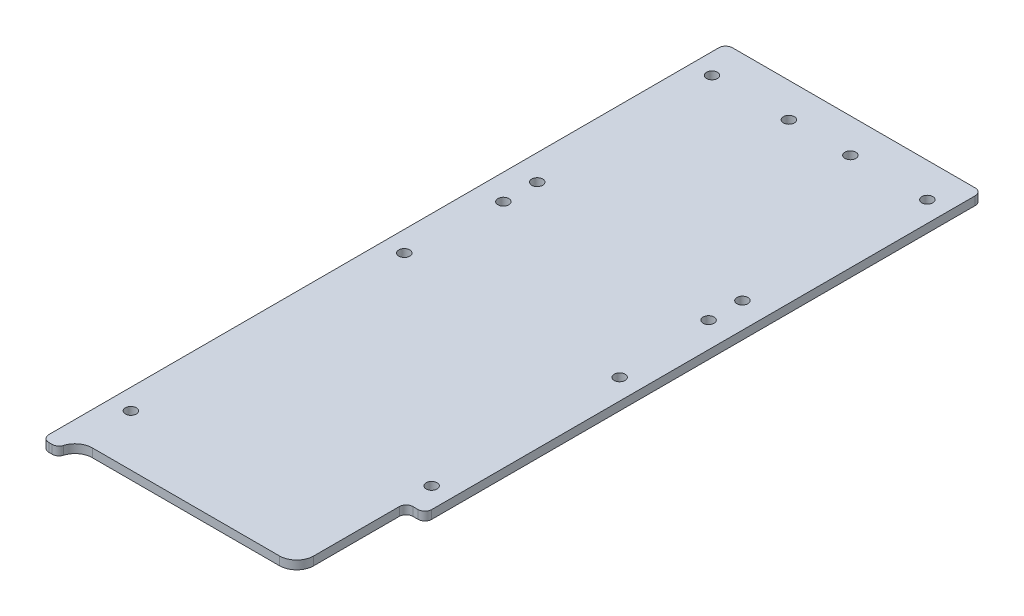
SolidWorks part; units mm, degrees
ref_plane "Front Plane" through (0, 0, 0) normal (0, 0, 1) x (1, 0, 0)
ref_plane "Top Plane" through (0, 0, 0) normal (0, 1, 0) x (1, 0, 0)
ref_plane "Right Plane" through (0, 0, 0) normal (1, 0, 0) x (0, 0, -1)
sketch "Sketch1" plane through (0, 0, 0) normal (0, 1, 0) x (1, 0, 0)
  line L0 (-39.9997, 0) -> (-39.9997, 114.3) construction
  line L1 (-47.625, 127) -> (47.625, 127)
  line L2 (-47.625, 127) -> (-47.625, -127)
  line L3 (-47.625, -127) -> (47.625, -127)
  line L4 (47.625, 127) -> (47.625, -127)
  line L5 (-47.625, 127) -> (47.625, -127) construction
  line L6 (-47.625, -127) -> (47.625, 127) construction
  line L7 (0, 0) -> (0, 127) construction
  line L8 (-39.9997, 0) -> (-39.9997, -101.6) construction
  line L9 (-39.9997, 0) -> (0, 0) construction
  line L10 (-41.275, -127) -> (-41.275, -120.65)
  line L11 (-41.275, -120.65) -> (41.275, -120.65)
  line L12 (41.275, -120.65) -> (41.275, -127)
  line L13 (-39.9997, 114.3) -> (-11.4247, 114.3) construction
  line L14 (39.9997, 114.3) -> (11.4247, 114.3) construction
  circle A0 centre (-39.9997, 114.3) radius 2.032
  circle A1 centre (-39.9997, 0) radius 2.032
  circle A2 centre (-39.9997, -101.6) radius 2.032
  circle A3 centre (39.9997, -101.6) radius 2.032
  circle A4 centre (39.9997, 0) radius 2.032
  circle A5 centre (39.9997, 114.3) radius 2.032
  circle A6 centre (-11.4247, 114.3) radius 2.032
  circle A7 centre (11.4247, 114.3) radius 2.032
  circle A8 centre (-39.9997, -69.85) radius 2.032
  circle A9 centre (39.9997, -69.85) radius 2.032
  point P0 (0, 0)
  dimension "D4" = 4.064
  dimension "D10" = 28.575
  dimension "D1" = 95.25
  dimension "D2" = 254
  dimension "D3" = 7.6253
  dimension "D5" = 12.7
  dimension "D6" = 25.4
  dimension "D7" = 6.35
  dimension "D8" = 6.35
  dimension "D9" = 6.35
  dimension "D11" = 69.85
extrude "Boss-Extrude1" add sketch "Sketch1" along normal blind 3.175 contours L4 L1 L2 L3 A4 A0 A1 A2 A3 A5 | A8 | A3 region at (0, 0, -2.6944) region at (39.9997, 0, 101.6) region at (-39.9997, 0, 69.85)
fillet "Fillet1" radius 2.54 4 edges at (-47.625, 1.5875, -127) (47.625, 1.5875, -127) (47.625, 1.5875, 127) (-47.625, 1.5875, 127)
fillet "Fillet2" radius 2.54 2 edges at (41.275, 1.5875, 127) (-41.275, 1.5875, 127)
fillet "Fillet3" radius 6.35 2 edges at (41.275, 1.5875, 120.65) (-41.275, 1.5875, 120.65)
sketch "Sketch2" plane through (0, 0, 0) normal (0, -1, 0) x (1, 0, 0)
  line L0 (41.9102, 131.8831) -> (41.9102, 109.8659) construction
  line L1 (41.9102, 109.8659) -> (41.9102, 106.3879) construction
  line L2 (41.9102, 83.271) -> (41.9102, 82.5325) construction
  line L3 (41.9102, 82.5325) -> (41.9102, 81.2514) construction
  line L4 (41.9102, 83.271) -> (41.9102, 106.3879) construction
  line L5 (41.9102, 131.8831) -> (41.9102, 109.8659)
  line L6 (41.9102, 109.8659) -> (41.9102, 106.3879)
  line L7 (41.9102, 83.271) -> (41.9102, 82.5325)
  line L8 (41.9102, 82.5325) -> (41.9102, 81.2514)
  line L9 (41.9102, 83.271) -> (41.9102, 106.3879)
  line L10 (41.9102, 81.2514) -> (47.625, 81.2514)
  line L11 (47.625, -124.46) -> (47.625, 124.46) construction
  line L12 (41.9102, 131.8831) -> (47.625, 131.8831)
  line L13 (47.625, 131.8831) -> (47.625, 81.2514)
  line L14 (40.6402, 79.9814) -> (48.895, 79.9814)
  line L15 (48.895, 133.1531) -> (48.895, 79.9814)
  line L16 (40.6402, 133.1531) -> (48.895, 133.1531)
  line L17 (40.6402, 133.1531) -> (40.6402, 109.8659)
  line L18 (40.6402, 109.8659) -> (40.6402, 106.3879)
  line L19 (40.6402, 83.271) -> (40.6402, 106.3879)
  line L20 (40.6402, 83.271) -> (40.6402, 82.5325)
  line L21 (40.6402, 82.5325) -> (40.6402, 79.9814)
  arc M7 (43.815, 127) -> (41.3809, 125.1857) centre (43.815, 124.46) ccw
  arc M8 (41.3809, 125.1857) -> (35.2956, 120.65) centre (35.2956, 127) cw
  line M18 (47.625, -124.46) -> (47.625, 124.46)
  dimension "D1" = 1.27
extrude "Cut-Extrude1" cut sketch "Sketch2" against normal through all contours L20 L21 L14 L10 L8 L7 L9 L19 M18 | L19 L9 L6 L5 L17 L18 M7 M8 | L13 L10 L8 L7 L9 L6 L5 L12 region at (41.6754, 0, 99.979)
fillet "Fillet4" radius 6.35 1 edges at (40.6402, 1.5875, 123.571)
fillet "Fillet5" radius 2.54 2 edges at (47.625, 1.5875, 79.9814) (40.6402, 1.5875, 79.9814)
sketch "Sketch3" plane through (0, 0, 0) normal (0, -1, 0) x (1, 0, 0)
  line L0 (-36.3103, -49.7791) -> (-39.9171, -49.7791) construction
  line L1 (-40.4251, -49.276) -> (-40.4251, -45.7043) construction
  line L2 (-35.8023, -45.7043) -> (-35.8023, -49.276) construction
  line L3 (-39.9171, -45.2013) -> (-36.3103, -45.2013) construction
  line L4 (-36.3103, -37.2027) -> (-39.9171, -37.2027) construction
  line L5 (-35.8023, -33.1279) -> (-35.8023, -36.6996) construction
  line L6 (-40.4251, -36.6996) -> (-40.4251, -33.1279) construction
  line L7 (-39.9171, -32.6249) -> (-36.3103, -32.6249) construction
  line L8 (36.2829, -32.6249) -> (39.8897, -32.6249) construction
  line L9 (40.3977, -33.1279) -> (40.3977, -36.6996) construction
  line L10 (39.8897, -37.2027) -> (36.2829, -37.2027) construction
  line L11 (35.7749, -36.6996) -> (35.7749, -33.1279) construction
  line L12 (36.2829, -45.2013) -> (39.8897, -45.2013) construction
  line L13 (35.7749, -49.276) -> (35.7749, -45.7043) construction
  line L14 (40.3977, -45.7043) -> (40.3977, -49.276) construction
  line L15 (39.8897, -49.7791) -> (36.2829, -49.7791) construction
  line L16 (-36.3103, -49.7791) -> (-39.9171, -49.7791)
  line L17 (-40.4251, -49.276) -> (-40.4251, -45.7043)
  line L18 (-35.8023, -45.7043) -> (-35.8023, -49.276)
  line L19 (-39.9171, -45.2013) -> (-36.3103, -45.2013)
  line L20 (-36.3103, -37.2027) -> (-39.9171, -37.2027)
  line L21 (-35.8023, -33.1279) -> (-35.8023, -36.6996)
  line L22 (-40.4251, -36.6996) -> (-40.4251, -33.1279)
  line L23 (-39.9171, -32.6249) -> (-36.3103, -32.6249)
  line L24 (36.2829, -32.6249) -> (39.8897, -32.6249)
  line L25 (40.3977, -33.1279) -> (40.3977, -36.6996)
  line L26 (39.8897, -37.2027) -> (36.2829, -37.2027)
  line L27 (35.7749, -36.6996) -> (35.7749, -33.1279)
  line L28 (36.2829, -45.2013) -> (39.8897, -45.2013)
  line L29 (35.7749, -49.276) -> (35.7749, -45.7043)
  line L30 (40.3977, -45.7043) -> (40.3977, -49.276)
  line L31 (39.8897, -49.7791) -> (36.2829, -49.7791)
  line L32 (-47.625, -25.836) -> (47.625, -25.836)
  line L33 (-47.625, -124.46) -> (-47.625, 124.46) construction
  line L34 (47.625, -124.46) -> (47.625, 77.4414) construction
  line L35 (0, -25.836) -> (0, -56.0686) construction
  line L38 (134.3604, -51.414) -> (184.1363, -51.414)
  line L39 (184.1363, -51.414) -> (184.1363, -43.4909)
  line L40 (184.1363, -43.4909) -> (182.3329, -43.4909)
  line L41 (181.8249, -42.9878) -> (181.8249, -39.4161)
  line L42 (182.3329, -38.9131) -> (184.1363, -38.9131)
  line L43 (184.1363, -38.9131) -> (184.1363, -30.9899)
  line L44 (184.1363, -30.9899) -> (134.3604, -30.9899)
  line L45 (134.3604, -30.9899) -> (133.3363, -32.0042)
  line L46 (133.3363, -32.0042) -> (132.3121, -30.9899)
  line L47 (132.3121, -30.9899) -> (70.8604, -30.9899)
  line L48 (70.8604, -30.9899) -> (69.8363, -32.0042)
  line L49 (69.8363, -32.0042) -> (68.8121, -30.9899)
  line L50 (68.8121, -30.9899) -> (7.3604, -30.9899)
  line L51 (7.3604, -30.9899) -> (6.3363, -32.0042)
  line L52 (6.3363, -32.0042) -> (5.3121, -30.9899)
  line L53 (5.3121, -30.9899) -> (-56.1396, -30.9899)
  line L54 (-56.1396, -30.9899) -> (-57.1637, -32.0042)
  line L55 (-57.1637, -32.0042) -> (-58.1879, -30.9899)
  line L56 (-58.1879, -30.9899) -> (-119.6396, -30.9899)
  line L57 (-119.6396, -30.9899) -> (-120.6637, -32.0042)
  line L58 (-120.6637, -32.0042) -> (-121.6879, -30.9899)
  line L59 (-121.6879, -30.9899) -> (-184.1637, -30.9899)
  line L60 (-184.1637, -30.9899) -> (-184.1637, -51.414)
  line L61 (-184.1637, -51.414) -> (-121.6879, -51.414)
  line L62 (-121.6879, -51.414) -> (-120.6637, -50.3998)
  line L63 (-120.6637, -50.3998) -> (-119.6396, -51.414)
  line L64 (-119.6396, -51.414) -> (-58.1879, -51.414)
  line L65 (-58.1879, -51.414) -> (-57.1637, -50.3998)
  line L66 (-57.1637, -50.3998) -> (-56.1396, -51.414)
  line L67 (-56.1396, -51.414) -> (5.3121, -51.414)
  line L68 (5.3121, -51.414) -> (6.3363, -50.3998)
  line L69 (6.3363, -50.3998) -> (7.3604, -51.414)
  line L70 (7.3604, -51.414) -> (68.8121, -51.414)
  line L71 (68.8121, -51.414) -> (69.8363, -50.3998)
  line L72 (69.8363, -50.3998) -> (70.8604, -51.414)
  line L73 (70.8604, -51.414) -> (132.3121, -51.414)
  line L74 (132.3121, -51.414) -> (133.3363, -50.3998)
  line L75 (133.3363, -50.3998) -> (134.3604, -51.414)
  line L76 (134.3604, -51.414) -> (184.1363, -51.414)
  line L77 (184.1363, -51.414) -> (184.1363, -43.4909)
  line L78 (184.1363, -43.4909) -> (182.3329, -43.4909)
  line L79 (181.8249, -42.9878) -> (181.8249, -39.4161)
  line L80 (182.3329, -38.9131) -> (184.1363, -38.9131)
  line L81 (184.1363, -38.9131) -> (184.1363, -30.9899)
  line L82 (184.1363, -30.9899) -> (134.3604, -30.9899)
  line L83 (134.3604, -30.9899) -> (133.3363, -32.0042)
  line L84 (133.3363, -32.0042) -> (132.3121, -30.9899)
  line L85 (132.3121, -30.9899) -> (70.8604, -30.9899)
  line L86 (70.8604, -30.9899) -> (69.8363, -32.0042)
  line L87 (69.8363, -32.0042) -> (68.8121, -30.9899)
  line L88 (68.8121, -30.9899) -> (7.3604, -30.9899)
  line L89 (7.3604, -30.9899) -> (6.3363, -32.0042)
  line L90 (6.3363, -32.0042) -> (5.3121, -30.9899)
  line L91 (5.3121, -30.9899) -> (-56.1396, -30.9899)
  line L92 (-56.1396, -30.9899) -> (-57.1637, -32.0042)
  line L93 (-57.1637, -32.0042) -> (-58.1879, -30.9899)
  line L94 (-58.1879, -30.9899) -> (-119.6396, -30.9899)
  line L95 (-119.6396, -30.9899) -> (-120.6637, -32.0042)
  line L96 (-120.6637, -32.0042) -> (-121.6879, -30.9899)
  line L97 (-121.6879, -30.9899) -> (-184.1637, -30.9899)
  line L98 (-184.1637, -30.9899) -> (-184.1637, -51.414)
  line L99 (-184.1637, -51.414) -> (-121.6879, -51.414)
  line L100 (-121.6879, -51.414) -> (-120.6637, -50.3998)
  line L101 (-120.6637, -50.3998) -> (-119.6396, -51.414)
  line L102 (-119.6396, -51.414) -> (-58.1879, -51.414)
  line L103 (-58.1879, -51.414) -> (-57.1637, -50.3998)
  line L104 (-57.1637, -50.3998) -> (-56.1396, -51.414)
  line L105 (-56.1396, -51.414) -> (5.3121, -51.414)
  line L106 (5.3121, -51.414) -> (6.3363, -50.3998)
  line L107 (6.3363, -50.3998) -> (7.3604, -51.414)
  line L108 (7.3604, -51.414) -> (68.8121, -51.414)
  line L109 (68.8121, -51.414) -> (69.8363, -50.3998)
  line L110 (69.8363, -50.3998) -> (70.8604, -51.414)
  line L111 (70.8604, -51.414) -> (132.3121, -51.414)
  line L112 (132.3121, -51.414) -> (133.3363, -50.3998)
  line L113 (133.3363, -50.3998) -> (134.3604, -51.414)
  line L1362 (-40.4251, -34.9138) -> (-35.8023, -34.9138)
  line L1857 (-38.1137, -32.6249) -> (-38.1137, -37.2027)
  line L1858 (-38.1137, -45.2013) -> (-38.1137, -49.7791)
  line L1859 (-40.4251, -47.4902) -> (-35.8023, -47.4902)
  circle A0 centre (-38.1137, -34.9138) radius 2.032
  circle A1 centre (-38.1137, -47.4902) radius 2.032
  circle A2 centre (38.1137, -47.4902) radius 2.032
  circle A3 centre (38.1137, -34.9138) radius 2.032
  ellipse E0 centre (-39.9171, -45.7043) end of major axis (-39.4091, -45.7043) minor radius 0.5031 (-39.9171, -45.2013) -> (-40.4251, -45.7043) ccw construction
  ellipse E1 centre (-39.9171, -49.276) end of major axis (-39.4091, -49.276) minor radius 0.5031 (-40.4251, -49.276) -> (-39.9171, -49.7791) ccw construction
  ellipse E2 centre (182.3329, -42.9878) end of major axis (182.8409, -42.9878) minor radius 0.5031 (181.8249, -42.9878) -> (182.3329, -43.4909) ccw
  ellipse E3 centre (182.3329, -39.4161) end of major axis (182.8409, -39.4161) minor radius 0.5031 (182.3329, -38.9131) -> (181.8249, -39.4161) ccw
  ellipse E4 centre (182.3329, -42.9878) end of major axis (182.8409, -42.9878) minor radius 0.5031 (181.8249, -42.9878) -> (182.3329, -43.4909) ccw
  ellipse E5 centre (182.3329, -39.4161) end of major axis (182.8409, -39.4161) minor radius 0.5031 (182.3329, -38.9131) -> (181.8249, -39.4161) ccw
  ellipse E6 centre (-36.3103, -49.276) end of major axis (-35.8023, -49.276) minor radius 0.5031 (-36.3103, -49.7791) -> (-35.8023, -49.276) ccw construction
  ellipse E7 centre (-36.3103, -45.7043) end of major axis (-35.8023, -45.7043) minor radius 0.5031 (-35.8023, -45.7043) -> (-36.3103, -45.2013) ccw construction
  ellipse E8 centre (-39.9171, -36.6996) end of major axis (-39.4091, -36.6996) minor radius 0.5031 (-40.4251, -36.6996) -> (-39.9171, -37.2027) ccw construction
  ellipse E9 centre (-36.3103, -36.6996) end of major axis (-35.8023, -36.6996) minor radius 0.5031 (-36.3103, -37.2027) -> (-35.8023, -36.6996) ccw construction
  ellipse E10 centre (-36.3103, -33.1279) end of major axis (-35.8023, -33.1279) minor radius 0.5031 (-35.8023, -33.1279) -> (-36.3103, -32.6249) ccw construction
  ellipse E11 centre (-39.9171, -33.1279) end of major axis (-39.4091, -33.1279) minor radius 0.5031 (-39.9171, -32.6249) -> (-40.4251, -33.1279) ccw construction
  ellipse E12 centre (39.8897, -33.1279) end of major axis (40.3977, -33.1279) minor radius 0.5031 (40.3977, -33.1279) -> (39.8897, -32.6249) ccw construction
  ellipse E13 centre (36.2829, -33.1279) end of major axis (36.7909, -33.1279) minor radius 0.5031 (36.2829, -32.6249) -> (35.7749, -33.1279) ccw construction
  ellipse E14 centre (39.8897, -36.6996) end of major axis (40.3977, -36.6996) minor radius 0.5031 (39.8897, -37.2027) -> (40.3977, -36.6996) ccw construction
  ellipse E15 centre (36.2829, -36.6996) end of major axis (36.7909, -36.6996) minor radius 0.5031 (35.7749, -36.6996) -> (36.2829, -37.2027) ccw construction
  ellipse E16 centre (36.2829, -45.7043) end of major axis (36.7909, -45.7043) minor radius 0.5031 (36.2829, -45.2013) -> (35.7749, -45.7043) ccw construction
  ellipse E17 centre (36.2829, -49.276) end of major axis (36.7909, -49.276) minor radius 0.5031 (35.7749, -49.276) -> (36.2829, -49.7791) ccw construction
  ellipse E18 centre (39.8897, -45.7043) end of major axis (40.3977, -45.7043) minor radius 0.5031 (40.3977, -45.7043) -> (39.8897, -45.2013) ccw construction
  ellipse E19 centre (39.8897, -49.276) end of major axis (40.3977, -49.276) minor radius 0.5031 (39.8897, -49.7791) -> (40.3977, -49.276) ccw construction
  ellipse E20 centre (-39.9171, -45.7043) end of major axis (-39.4091, -45.7043) minor radius 0.5031 (-39.9171, -45.2013) -> (-40.4251, -45.7043) ccw
  ellipse E21 centre (-39.9171, -49.276) end of major axis (-39.4091, -49.276) minor radius 0.5031 (-40.4251, -49.276) -> (-39.9171, -49.7791) ccw
  ellipse E22 centre (-36.3103, -49.276) end of major axis (-35.8023, -49.276) minor radius 0.5031 (-36.3103, -49.7791) -> (-35.8023, -49.276) ccw
  ellipse E23 centre (-36.3103, -45.7043) end of major axis (-35.8023, -45.7043) minor radius 0.5031 (-35.8023, -45.7043) -> (-36.3103, -45.2013) ccw
  ellipse E24 centre (-39.9171, -36.6996) end of major axis (-39.4091, -36.6996) minor radius 0.5031 (-40.4251, -36.6996) -> (-39.9171, -37.2027) ccw
  ellipse E25 centre (-36.3103, -36.6996) end of major axis (-35.8023, -36.6996) minor radius 0.5031 (-36.3103, -37.2027) -> (-35.8023, -36.6996) ccw
  ellipse E26 centre (-36.3103, -33.1279) end of major axis (-35.8023, -33.1279) minor radius 0.5031 (-35.8023, -33.1279) -> (-36.3103, -32.6249) ccw
  ellipse E27 centre (-39.9171, -33.1279) end of major axis (-39.4091, -33.1279) minor radius 0.5031 (-39.9171, -32.6249) -> (-40.4251, -33.1279) ccw
  ellipse E28 centre (39.8897, -33.1279) end of major axis (40.3977, -33.1279) minor radius 0.5031 (40.3977, -33.1279) -> (39.8897, -32.6249) ccw
  ellipse E29 centre (36.2829, -33.1279) end of major axis (36.7909, -33.1279) minor radius 0.5031 (36.2829, -32.6249) -> (35.7749, -33.1279) ccw
  ellipse E30 centre (39.8897, -36.6996) end of major axis (40.3977, -36.6996) minor radius 0.5031 (39.8897, -37.2027) -> (40.3977, -36.6996) ccw
  ellipse E31 centre (36.2829, -36.6996) end of major axis (36.7909, -36.6996) minor radius 0.5031 (35.7749, -36.6996) -> (36.2829, -37.2027) ccw
  ellipse E32 centre (36.2829, -45.7043) end of major axis (36.7909, -45.7043) minor radius 0.5031 (36.2829, -45.2013) -> (35.7749, -45.7043) ccw
  ellipse E33 centre (36.2829, -49.276) end of major axis (36.7909, -49.276) minor radius 0.5031 (35.7749, -49.276) -> (36.2829, -49.7791) ccw
  ellipse E34 centre (39.8897, -45.7043) end of major axis (40.3977, -45.7043) minor radius 0.5031 (40.3977, -45.7043) -> (39.8897, -45.2013) ccw
  ellipse E35 centre (39.8897, -49.276) end of major axis (40.3977, -49.276) minor radius 0.5031 (39.8897, -49.7791) -> (40.3977, -49.276) ccw
  dimension "D2" = 4.064
  dimension "D1" = 0
extrude "Cut-Extrude2" cut sketch "Sketch3" against normal through all contours A0 | A1 | A2 | A3
